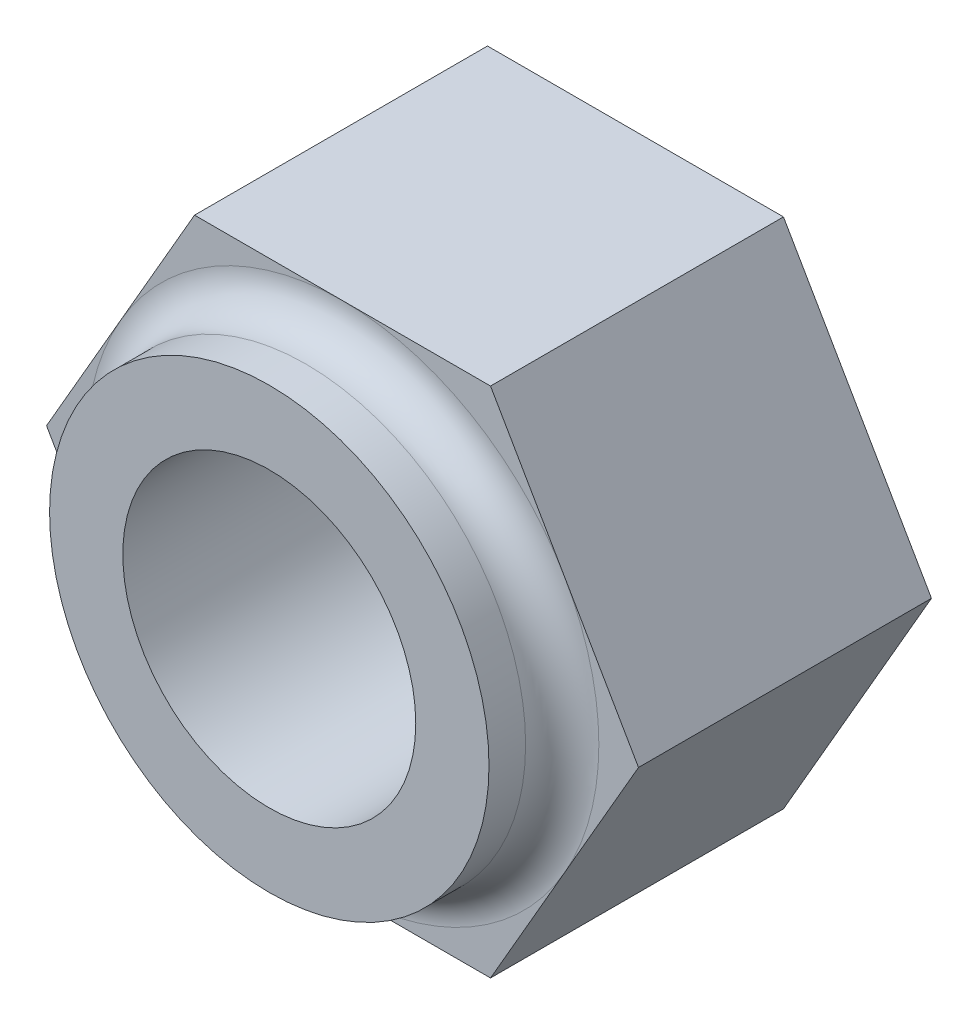
SolidWorks part; units mm, degrees
material "AISI 304"
ref_plane "前视基准面" through (0, 0, 0) normal (0, 0, 1) x (1, 0, 0)
ref_plane "上视基准面" through (0, 0, 0) normal (0, 1, 0) x (1, 0, 0)
ref_plane "右视基准面" through (0, 0, 0) normal (1, 0, 0) x (0, 0, -1)
other "Configuration Table"
sketch "草图1" plane through (0, 0, 0) normal (0, 0, 1) x (1, 0, 0)
  line L0 (0, 0) -> (4.0415, 0) construction
  line L1 (4.0415, 0) -> (2.0207, 3.5)
  line L2 (2.0207, 3.5) -> (-2.0207, 3.5)
  line L3 (-2.0207, 3.5) -> (-4.0415, 0)
  line L4 (-4.0415, 0) -> (-2.0207, -3.5)
  line L5 (-2.0207, -3.5) -> (2.0207, -3.5)
  line L6 (2.0207, -3.5) -> (4.0415, 0)
  circle A0 centre (0, 0) radius 3.5 construction
  circle A1 centre (0, 0) radius 2
  dimension "D2" = 4
  dimension "D1" = 7
extrude "凸台-拉伸1" add sketch "草图1" along normal blind 5
sketch "草图2" plane through (0, 0, 5) normal (0, 0, 1) x (1, 0, 0)
  line L0 (0, 0) -> (4.0415, 0) construction
  line L1 (4.0415, 0) -> (2.0207, 3.5)
  line L2 (2.0207, 3.5) -> (-2.0207, 3.5)
  line L3 (-2.0207, 3.5) -> (-4.0415, 0)
  line L4 (-4.0415, 0) -> (-2.0207, -3.5)
  line L5 (-2.0207, -3.5) -> (2.0207, -3.5)
  line L6 (2.0207, -3.5) -> (4.0415, 0)
  circle A0 centre (0, 0) radius 3
  circle A1 centre (0, 0) radius 3.5 construction
  dimension "D1" = 6
  dimension "D2" = 7
extrude "切除-拉伸1" cut sketch "草图2" against normal blind 1
fillet "圆角1" radius 0.5 1 edges at (3, 0, 4)
